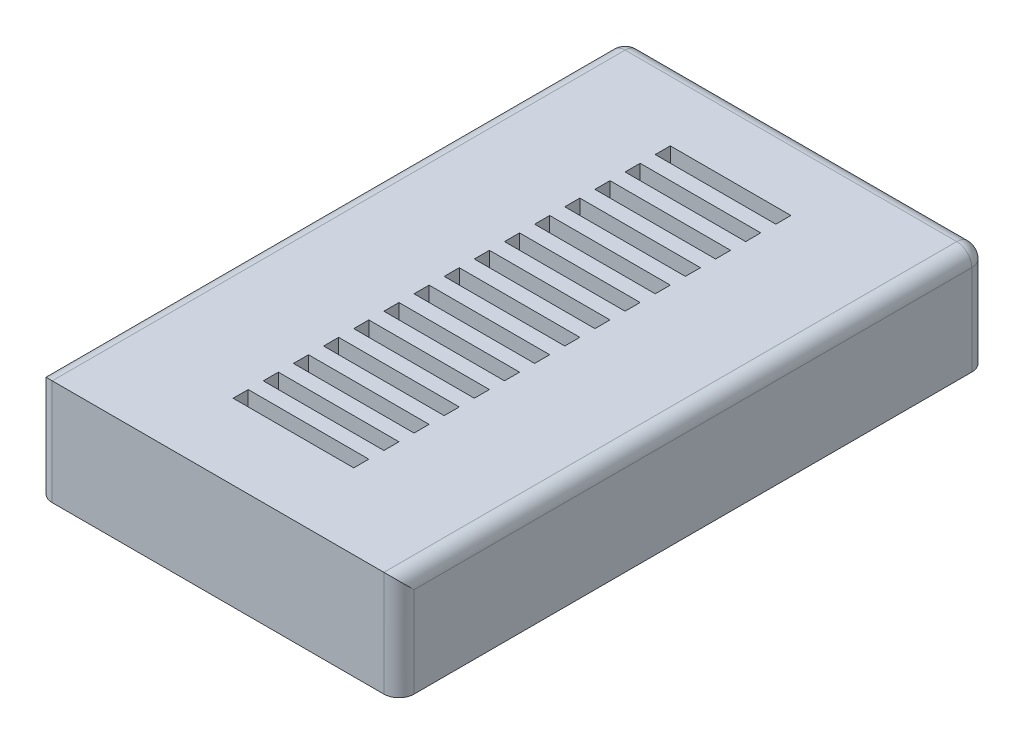
SolidWorks part; units mm, degrees
ref_plane "Ebene vorne" through (0, 0, 0) normal (0, 0, 1) x (1, 0, 0)
ref_plane "Ebene oben" through (0, 0, 0) normal (0, 1, 0) x (1, 0, 0)
ref_plane "Ebene rechts" through (0, 0, 0) normal (1, 0, 0) x (0, 0, -1)
sketch "Skizze1" plane through (0, 0, 0) normal (0, 0, 1) x (1, 0, 0)
  line L1 (0, 0) -> (20, 0)
  line L2 (0, 0) -> (0, 5)
  line L3 (0, 5) -> (20, 5)
  line L4 (20, 0) -> (20, 5)
  dimension "D1" = 5
  dimension "D2" = 20
extrude "Aufsatz-Linear austragen1" add sketch "Skizze1" along normal blind 35
shell "Wandung1" thickness 2 removed face at (10, 0, 17.5) outward yes
fillet "Verrundung1" radius 1 7 edges at (-2, 3.5, -2) (-2, 3.5, 37) (22, 3.5, 37) (22, 3.5, -2) (22, 7, 17.5) (-2, 7, 17.5) (10, 7, -2)
ref_plane "Ebene1" through (0, 0, 0) normal (0, -1, 0) x (-1, 0, 0)
fillet "Verrundung3" radius 1 4 edges at (10, 0, 0) (0, 0, 17.5) (10, 0, 35) (20, 0, 17.5)
sketch "Skizze6" plane through (0, 5, 0) normal (0, -1, 0) x (1, 0, 0)
  line L1 (20, 35) -> (0, 35)
  line L2 (20, 35) -> (20, 0)
  line L3 (20, 0) -> (0, 0)
  line L4 (0, 35) -> (0, 0)
  line L5 (18, 33) -> (2, 33)
  line L6 (18, 33) -> (18, 2)
  line L7 (18, 2) -> (2, 2)
  line L8 (2, 33) -> (2, 2)
  dimension "D1" = 2
  dimension "D2" = 2
  dimension "D3" = 2
  dimension "D4" = 2
extrude "Aufsatz-Linear austragen2" add sketch "Skizze6" along normal blind 1
sketch "Skizze7" plane through (0, 5, 0) normal (0, -1, 0) x (1, 0, 0)
  line L1 (14, 17) -> (6, 17)
  line L2 (14, 17) -> (14, 18)
  line L3 (14, 18) -> (6, 18)
  line L4 (6, 17) -> (6, 18)
  line L6 (18, 2) -> (18, 33) construction
  line L8 (2, 2) -> (18, 2) construction
  point P4 (14, 17.5)
  dimension "D1" = 1
  dimension "D2" = 15.5
  dimension "D3" = 8
  dimension "D4" = 4
extrude "Schnitt-Linear austragen1" cut sketch "Skizze7" against normal up to surface (2 mm away) up to face at (10, 7, 18)
pattern_linear "Lineares Muster1" count 8 spacing 2 along (0, 0, -1) count 8 spacing 2 along (0, 0, 1) of "Schnitt-Linear austragen1"
